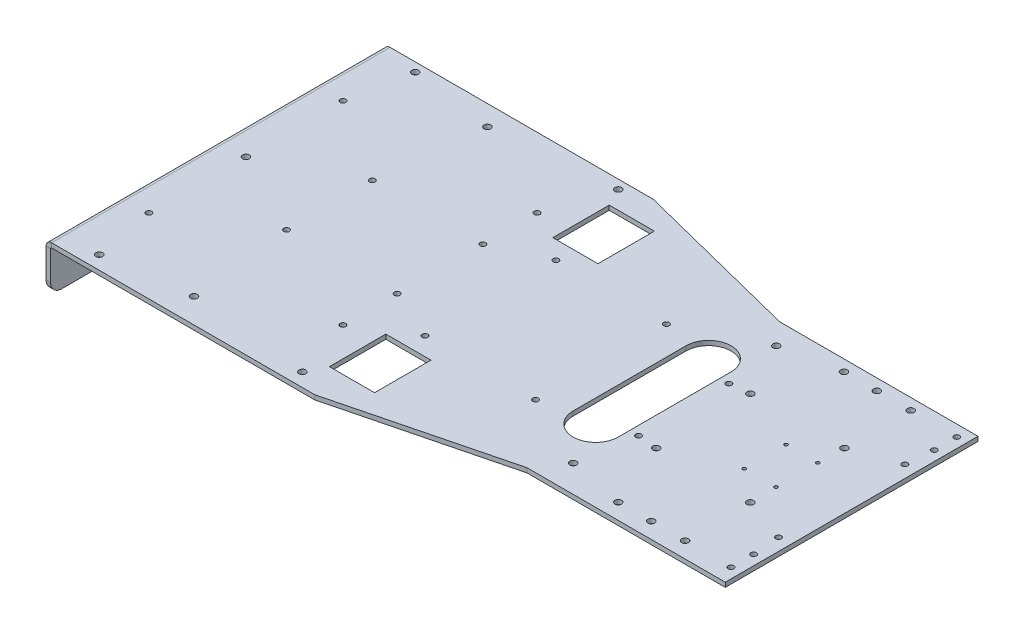
SolidWorks part; units mm, degrees
note: The reader was unsure of these and kept them because the rebuilt part matched: flange length of "Brida de arista1".
ref_plane "Alzado" through (0, 0, 0) normal (0, 0, 1) x (1, 0, 0)
ref_plane "Planta" through (0, 0, 0) normal (0, 1, 0) x (1, 0, 0)
ref_plane "Vista lateral" through (0, 0, 0) normal (1, 0, 0) x (0, 0, -1)
sketch "Croquis base" plane through (0, 0, 0) normal (0, 1, 0) x (1, 0, 0)
  line L0 (52.1, 75) -> (52.1, -75) construction
  line L1 (-140, 75) -> (-22.9, 75)
  line L2 (-140, 75) -> (-140, -75)
  line L3 (-140, -75) -> (-22.9, -75)
  line L4 (140, 56) -> (140, -56)
  line L5 (-22.9, 75) -> (-22.9, -75) construction
  line L6 (52.1, 56) -> (140, 56)
  line L7 (52.1, -56) -> (140, -56)
  line L8 (-22.9, 75) -> (52.1, 56)
  line L9 (-22.9, -75) -> (52.1, -56)
  point P0 (0, 0)
  dimension "D1" = 280
  dimension "D2" = 150
  dimension "D3" = 87.9
  dimension "D4" = 162.9
  dimension "D5" = 19
  dimension "D6" = 19
  dimension "D7" = 112
base flange "Brida base1" sketch "Croquis base" thickness 2 reverse thickness direction no parameters "D1"=0.7366
sketch "Croquis9" plane through (0, 0, 0) normal (0, 1, 0) x (1, 0, 0)
  line L0 (-139.4208, 1.0136) -> (140.5792, 1.0136) construction
  line L1 (-139.4208, -68.9864) -> (-34.4208, -68.9864) construction
  line L2 (-124.4208, 76.0136) -> (-124.4208, -73.9864) construction
  line L3 (-34.4208, 76.0136) -> (-34.4208, -73.9864) construction
  line L4 (140.5792, -48.9864) -> (85.5792, -48.9864) construction
  line L5 (-30.4208, -35.9864) -> (-10.4208, -35.9864)
  line L6 (-30.4208, -35.9864) -> (-30.4208, -60.9864)
  line L7 (-30.4208, -60.9864) -> (-10.4208, -60.9864)
  line L8 (-10.4208, -35.9864) -> (-10.4208, -60.9864)
  line L9 (-30.4208, -35.9864) -> (-10.4208, -60.9864) construction
  line L10 (-30.4208, -60.9864) -> (-10.4208, -35.9864) construction
  line L11 (85.5792, 57.0136) -> (85.5792, -54.9864) construction
  line L12 (-139.4208, -41.9864) -> (140.5792, -41.9864) construction
  line L13 (-139.4208, -17.9864) -> (-43.4208, -17.9864) construction
  line L14 (52.6792, -54.9864) -> (25.6792, -54.9864) construction
  line L15 (52.6792, -54.9864) -> (52.6792, 1.0136) construction
  line L16 (140.5792, -19.8464) -> (73.2192, -19.8464) construction
  line L17 (60.5792, 26.0136) -> (60.5792, -23.9864)
  line L18 (100.6792, -8.2364) -> (114.6792, -8.2364) construction
  line L19 (-30.4208, 38.0136) -> (-10.4208, 38.0136)
  line L20 (-30.4208, 38.0136) -> (-30.4208, 63.0136)
  line L21 (-10.4208, 38.0136) -> (-10.4208, 63.0136)
  line L22 (-30.4208, 63.0136) -> (-10.4208, 63.0136)
  line L23 (40.5792, -23.9864) -> (40.5792, 26.0136)
  line L24 (-140, 75) -> (-140, -75) construction
  line L25 (-140, -75) -> (-22.9, -75) construction
  circle A0 centre (85.5792, -48.9864) radius 1.5
  circle A1 centre (100.1792, -48.9864) radius 1.5
  circle A2 centre (115.1792, -48.9864) radius 1.5
  circle A3 centre (135.5792, -48.9864) radius 1.25
  circle A4 centre (-124.4208, -68.9864) radius 1.5
  circle A5 centre (-34.4208, -68.9864) radius 1.5
  circle A6 centre (-87.4208, -64) radius 1.5
  circle A7 centre (-129.4208, -41.9864) radius 1.25
  circle A8 centre (-43.4208, -41.9864) radius 1.25
  circle A9 centre (60.5792, -43.9864) radius 1.5
  circle A10 centre (135.5792, -38.9864) radius 1.25
  circle A11 centre (134.5792, -26.9864) radius 1.25
  circle A12 centre (-92.4208, -17.9864) radius 1.25
  circle A13 centre (-43.4208, -17.9864) radius 1.25
  circle A14 centre (-21.0758, -27.9864) radius 1.25
  circle A15 centre (27.9242, -27.9864) radius 1.25
  circle A16 centre (64.5792, -18.9864) radius 1.25
  arc A17 (40.5792, -23.9864) -> (60.5792, -23.9864) centre (50.5792, -23.9864) ccw
  circle A18 centre (114.9392, -19.8464) radius 1.5
  circle A19 centre (73.2192, -19.8464) radius 1.5
  circle A20 centre (100.6792, -8.2364) radius 0.75
  circle A21 centre (114.6792, -8.2364) radius 0.75
  circle A22 centre (-124.4208, 71.0136) radius 1.5
  circle A23 centre (-129.4208, 44.0136) radius 1.25
  circle A24 centre (-87.4208, 66.0272) radius 1.5
  circle A25 centre (-92.4208, 20.0136) radius 1.25
  circle A26 centre (-43.4208, 20.0136) radius 1.25
  circle A27 centre (-43.4208, 44.0136) radius 1.25
  circle A28 centre (-34.4208, 71.0136) radius 1.5
  circle A29 centre (-21.0758, 30.0136) radius 1.25
  circle A30 centre (115.1792, 51.0136) radius 1.5
  circle A31 centre (27.9242, 30.0136) radius 1.25
  arc A32 (40.5792, 26.0136) -> (60.5792, 26.0136) centre (50.5792, 26.0136) cw
  circle A33 centre (64.5792, 21.0136) radius 1.25
  circle A34 centre (73.2192, 21.8736) radius 1.5
  circle A35 centre (60.5792, 46.0136) radius 1.5
  circle A36 centre (85.5792, 51.0136) radius 1.5
  circle A37 centre (100.1792, 51.0136) radius 1.5
  circle A38 centre (100.6792, 10.2636) radius 0.75
  circle A39 centre (114.6792, 10.2636) radius 0.75
  circle A40 centre (114.9392, 21.8736) radius 1.5
  circle A41 centre (134.5792, 29.0136) radius 1.25
  circle A42 centre (135.5792, 41.0136) radius 1.25
  circle A43 centre (135.5792, 51.0136) radius 1.25
  circle A44 centre (-129.4208, 1.0136) radius 1.5
  point P8 (-20.4208, -48.4864)
  point P96 (40.5792, 1.0136)
  point P98 (60.5792, 1.0136)
  dimension "D13" = 10
  dimension "D17" = 3
  dimension "D18" = 2.5
  dimension "D19" = 1.5
  dimension "D21" = 3
  dimension "D1" = 90
  dimension "D2" = 25
  dimension "D3" = 20
  dimension "D4" = 14.6
  dimension "D5" = 15
  dimension "D6" = 20.4
  dimension "D7" = 86
  dimension "D8" = 49
  dimension "D9" = 8
  dimension "D10" = 9.345
  dimension "D11" = 27
  dimension "D12" = 11.9
  dimension "D14" = 25
  dimension "D15" = 41.72
  dimension "D16" = 14
  dimension "D20" = 20
  dimension "D22" = 52.5792
  dimension "D23" = 11
  dimension "D24" = 8.4792
extrude "Cortar-Extruir2" cut sketch "Croquis9" against normal through all normal cut yes
edge flange "Brida de arista1" sketch "Croquis12" flange angle 90 flange length 18.4 flange position material outside bend radius 0.5 thickness 2 relief rectangular parameters "D6"=10
sketch "Croquis12" plane through (-140, -2, 0) normal (-1, 0, 0) x (0, 0, -1)
  line L2 (-75, 0) -> (-75, 18.4)
  line L3 (-75, 18.4) -> (75, 18.4)
  line L4 (75, 18.4) -> (75, 0)
  line L7 (75, 0) -> (-75, 0) construction
  line L8 (75, 0) -> (-75, 0)
bend "Pliegue de arista1" bend radius 0.5 bend angle 90 parameters "D5"=1
sketch "Croquis13" plane through (-142, 0, 0) normal (-1, 0, 0) x (0, 0, 1)
  line L0 (-75, -20.4) -> (75, -20.4) construction
  line L1 (-50, -10.9) -> (50, -10.9)
  line L2 (-50, -10.9) -> (-50, -17.9)
  line L3 (-50, -17.9) -> (50, -17.9)
  line L4 (50, -10.9) -> (50, -17.9)
  line L5 (75, -20.4) -> (75, -2.5) construction
  line L6 (-75, -14.4) -> (75, -14.4) construction
  line L7 (-75, -2.5) -> (-75, -20.4) construction
  circle A0 centre (55, -14.4) radius 1.5
  circle A1 centre (-55, -14.4) radius 1.5
  point P16 (-50, -14.4)
  point P17 (50, -14.4)
  dimension "D7" = 3
  dimension "D1" = 7
  dimension "D2" = 100
  dimension "D3" = 2.5
  dimension "D4" = 25
  dimension "D5" = 5
  dimension "D6" = 5
extrude "Cortar-Extruir3" cut sketch "Croquis13" against normal blind 10
fillet "Redondeo2" radius 5 2 edges at (-141, -20.4, 75) (-141, -20.4, -75)
sketch "Líneas de pliegue1" [suppressed] plane through (0, 0, 0) normal (0, 1, 0) x (1, 0, 0)
sketch "Cuadro delimitador1" [suppressed] plane through (0, 0, 0) normal (0, 1, 0) x (1, 0, 0)
sheet metal parameters "Chapa metálica3" thickness 2 parameters "D1"=0.7366
flat pattern "Chapa desplegada3" [suppressed]
sketch "Líneas de pliegue2" plane through (0, 0, 0) normal (0, 1, 0) x (1, 0, 0)
sketch3d "Cuadro delimitador2" [suppressed]
  line L0 (-140, -75, 0) -> (140, -75, 0) construction
  line L1 (-140, 75, 0) -> (140, 75, 0) construction
  line L2 (-140, -75, 0) -> (-140, 75, 0) construction
  line L3 (140, -75, 0) -> (140, 75, 0) construction
sheet metal parameters "Chapa metálica4" thickness 2 parameters "D1"=0.7366
flat pattern "Chapa desplegada3"
sketch "Líneas de pliegue2" plane through (0, 0, 0) normal (0, 1, 0) x (1, 0, 0)
sketch3d "Cuadro delimitador2" [suppressed]
  line L0 (140, -75, 0) -> (-140, -75, 0) construction
  line L1 (140, 75, 0) -> (-140, 75, 0) construction
  line L2 (140, -75, 0) -> (140, 75, 0) construction
  line L3 (-140, -75, 0) -> (-140, 75, 0) construction
sheet metal parameters "Chapa metálica5" thickness 2 parameters "D1"=0.7366
flat pattern "Chapa desplegada3"
sketch "Líneas de pliegue2" plane through (0, 0, 0) normal (0, 1, 0) x (1, 0, 0)
  line L0 (-140.6781, 75) -> (-140.6781, -75) construction
  line L1 (-140.6781, 75) -> (-140.6781, -75) construction
sketch3d "Cuadro delimitador2" [suppressed]
  line L0 (140, -75, 0) -> (-159.7562, -75, 0) construction
  line L1 (140, 75, 0) -> (-159.7562, 75, 0) construction
  line L2 (140, -75, 0) -> (140, 75, 0) construction
  line L3 (-159.7562, -75, 0) -> (-159.7562, 75, 0) construction
bend of the flat pattern "Aplanar-<Pliegue de arista1>1"
sheet metal parameters "Chapa metálica6" thickness 2 parameters "D1"=0.7366
flat pattern "Chapa desplegada3"
sketch "Líneas de pliegue2" plane through (0, 0, 0) normal (0, 1, 0) x (1, 0, 0)
  line L0 (-140.6781, 75) -> (-140.6781, -75) construction
  line L1 (-140.6781, 75) -> (-140.6781, -75) construction
sketch3d "Cuadro delimitador2" [suppressed]
  line L0 (-159.7562, -75, 0) -> (140, -75, 0) construction
  line L1 (-159.7562, 75, 0) -> (140, 75, 0) construction
  line L2 (-159.7562, -75, 0) -> (-159.7562, 75, 0) construction
  line L3 (140, -75, 0) -> (140, 75, 0) construction
bend of the flat pattern "Aplanar-<Pliegue de arista1>1"
